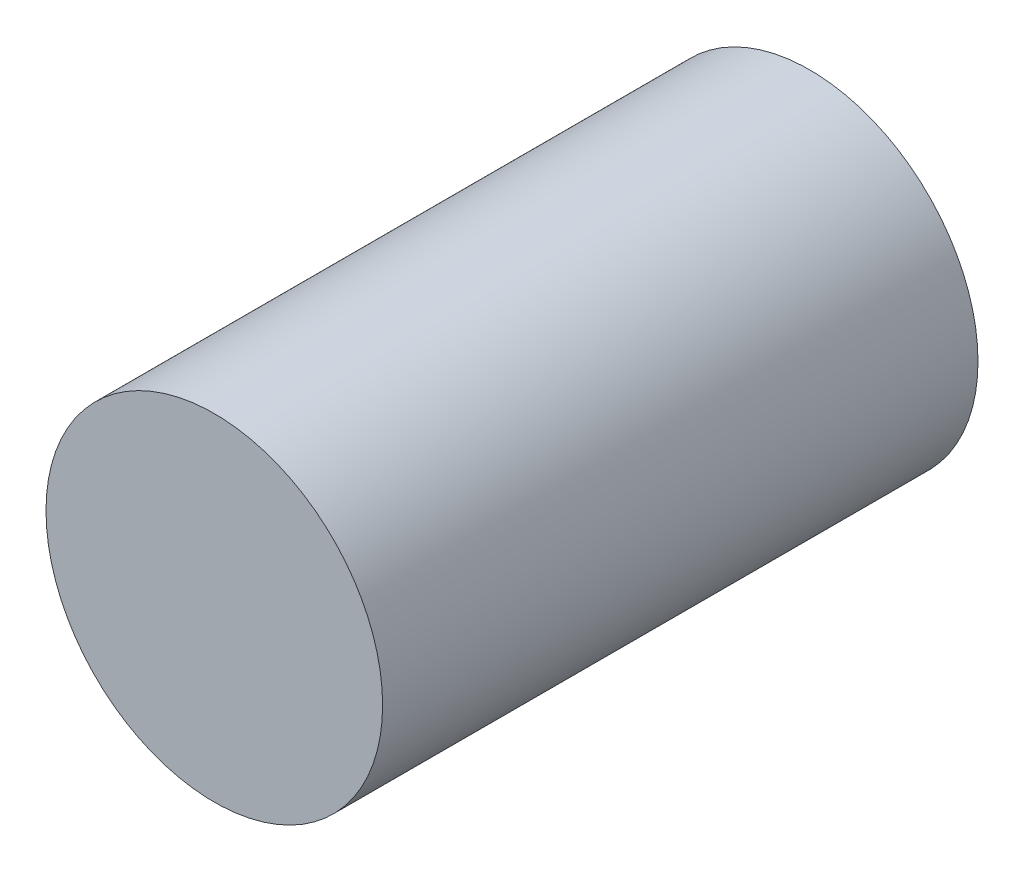
SolidWorks part; units mm, degrees
ref_plane "Front Plane" through (0, 0, 0) normal (0, 0, 1) x (1, 0, 0)
ref_plane "Top Plane" through (0, 0, 0) normal (0, 1, 0) x (1, 0, 0)
ref_plane "Right Plane" through (0, 0, 0) normal (1, 0, 0) x (0, 0, -1)
sketch "Sketch1" plane through (0, 0, 0) normal (0, 0, 1) x (1, 0, 0)
  circle A0 centre (0, 0) radius 33
  dimension "D1" = 66
extrude "Boss-Extrude1" add sketch "Sketch1" along normal blind 116.74
